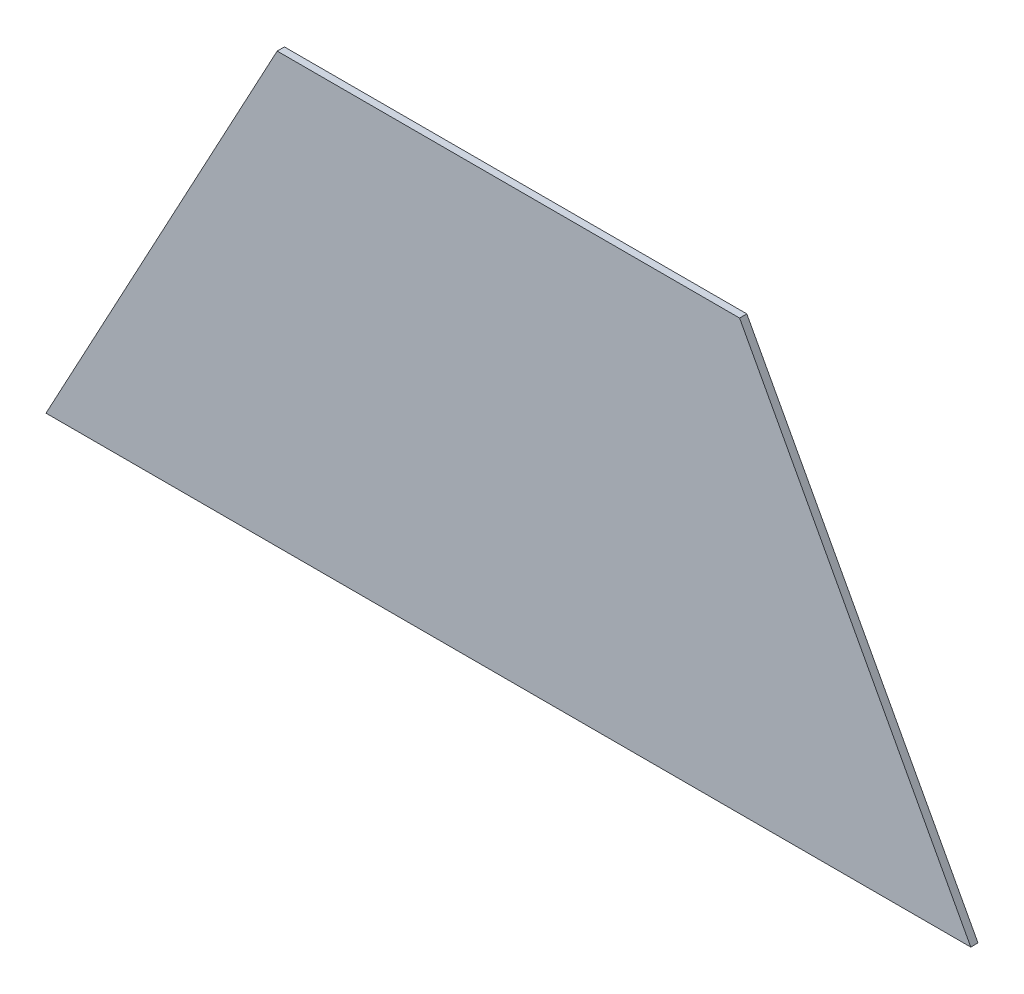
SolidWorks part; units mm, degrees
material "Printed Circuit Board"
ref_plane "Front Plane" through (0, 0, 0) normal (0, 0, 1) x (1, 0, 0)
ref_plane "Top Plane" through (0, 0, 0) normal (0, 1, 0) x (1, 0, 0)
ref_plane "Right Plane" through (0, 0, 0) normal (1, 0, 0) x (0, 0, -1)
sketch "Sketch1" plane through (0, 0, 0) normal (0, 0, 1) x (1, 0, 0)
  line L0 (0, 0) -> (203.2, 0)
  line L1 (203.2, 0) -> (101.6, 188.6145)
  line L2 (101.6, 188.6145) -> (0, 188.6145)
  line L3 (0, 188.6145) -> (-101.6, 188.6145)
  line L4 (-101.6, 188.6145) -> (-203.2, 0)
  line L5 (-203.2, 0) -> (0, 0)
  line L6 (0, 0) -> (0, 188.6145) construction
extrude "Extrude1" add sketch "Sketch1" along normal mid plane 3.175
